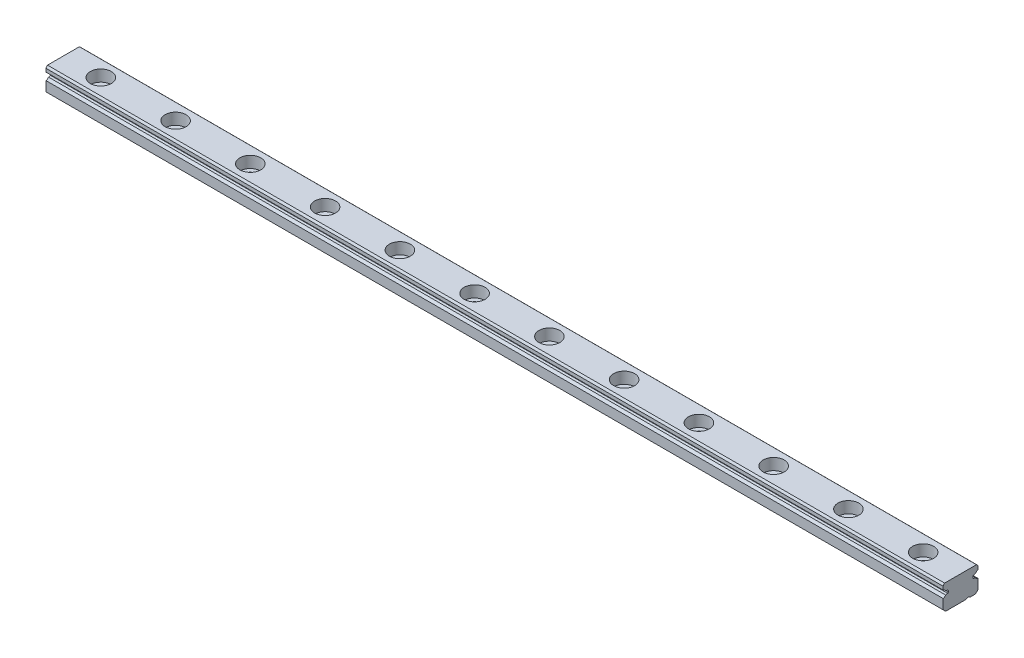
SolidWorks part; units mm, degrees
ref_plane "Front Plane" through (0, 0, 0) normal (0, 0, 1) x (1, 0, 0)
ref_plane "Top Plane" through (0, 0, 0) normal (0, 1, 0) x (1, 0, 0)
ref_plane "Right Plane" through (0, 0, 0) normal (1, 0, 0) x (0, 0, -1)
sketch "Sketch1" plane through (0, 0, 0) normal (1, 0, 0) x (0, 0, -1)
  line L0 (-3.5, 0.5) -> (-3, 0)
  line L1 (-3, 0) -> (3, 0)
  line L2 (3, 0) -> (3.5, 0.5)
  line L3 (3.5, 0.5) -> (3.5, 2.4652)
  line L4 (2.9999, 2.826) -> (2.572, 2.9015)
  line L5 (2.45, 3.051) -> (2.45, 3.349)
  line L6 (2.572, 3.4985) -> (2.9999, 3.574)
  line L7 (3.5, 3.9348) -> (3.5, 4.6)
  line L8 (3.2, 5) -> (-3.2, 5)
  line L9 (-3.5, 4.6) -> (-3.5, 3.9348)
  line L10 (-2.9999, 3.574) -> (-2.572, 3.4985)
  line L11 (-2.45, 3.349) -> (-2.45, 3.051)
  line L12 (-2.572, 2.9015) -> (-2.9999, 2.826)
  line L13 (-3.5, 2.4652) -> (-3.5, 0.5)
  arc A0 (3.5, 2.4652) -> (2.9999, 2.826) centre (3.65, 3.2) cw
  arc A1 (2.572, 2.9015) -> (2.45, 3.051) centre (2.8118, 3.2216) cw
  arc A2 (2.45, 3.349) -> (2.572, 3.4985) centre (2.8118, 3.1784) cw
  arc A3 (2.9999, 3.574) -> (3.5, 3.9348) centre (3.65, 3.2) cw
  arc A4 (3.5, 4.6) -> (3.2, 5) centre (2.7421, 4.344) ccw
  arc A5 (-3.2, 5) -> (-3.5, 4.6) centre (-2.7421, 4.344) ccw
  arc A6 (-3.5, 3.9348) -> (-2.9999, 3.574) centre (-3.65, 3.2) cw
  arc A7 (-2.572, 3.4985) -> (-2.45, 3.349) centre (-2.8118, 3.1784) cw
  arc A8 (-2.45, 3.051) -> (-2.572, 2.9015) centre (-2.8118, 3.2216) cw
  arc A9 (-2.9999, 2.826) -> (-3.5, 2.4652) centre (-3.65, 3.2) cw
extrude "Extrude1" add sketch "Sketch1" along normal blind 180
sketch "Sketch2" plane through (0, 0, 0) normal (0, 0, -1) x (-1, 0, 0)
  line L0 (-7.5, 5) -> (-5.4, 5)
  line L1 (-5.4, 5) -> (-5.4, 2.7)
  line L2 (-5.4, 2.7) -> (-6.3, 2.7)
  line L3 (-6.3, 2.7) -> (-6.3, 0.2)
  line L4 (-6.3, 0.2) -> (-6.1, 0)
  line L5 (-6.1, 0) -> (-7.5, 0)
  line L6 (-180, 5) -> (0, 5) construction
  line L7 (-7.5, 0) -> (-7.5, 5) construction
  line L8 (-180, 0) -> (0, 0) construction
  line L9 (0, 2.4652) -> (0, 0.5) construction
  line L10 (-7.5, 5) -> (-7.5, 0)
  dimension "D1" = 7.5
  dimension "D2" = 2.4
  dimension "D3" = 2.8
  dimension "D4" = 4.2
  dimension "D5" = 2.3
  dimension "D6" = 45
revolve "Cut-Revolve1" cut sketch "Sketch2" angle 360 about L7 reverse direction yes
sketch "Sketch3" plane through (45, 0, 0) normal (0, 0, -1) x (-1, 0, 0)
  line L0 (-127.5, 5) -> (-125.4, 5)
  line L1 (-125.4, 5) -> (-125.4, 2.7)
  line L2 (-125.4, 2.7) -> (-126.3, 2.7)
  line L3 (-126.3, 2.7) -> (-126.3, 0.2)
  line L4 (-126.3, 0.2) -> (-126.1, 0)
  line L5 (-126.1, 0) -> (-127.5, 0)
  line L6 (-135, 0) -> (45, 0) construction
  line L7 (-127.5, 0) -> (-127.5, 5) construction
  line L8 (-135, 5) -> (45, 5) construction
  line L9 (-135, 2.4652) -> (-135, 0.5) construction
  line L10 (-127.5, 5) -> (-127.5, 0)
  dimension "D1" = 7.5
  dimension "D2" = 2.4
  dimension "D3" = 2.8
  dimension "D4" = 45
  dimension "D5" = 4.2
  dimension "D6" = 2.3
revolve "Cut-Revolve2" cut sketch "Sketch3" angle 360 about L7 reverse direction yes
sketch "Sketch6" plane through (0, 0, 0) normal (1, 0, 0) x (0, 0, -1)
  circle A0 centre (1.5, -0.3) radius 0.5
extrude "Extrude2" cut sketch "Sketch6" along normal through all
ref_axis "Axis1" through (-3, 0, 0) along (1, 0, 0)
pattern_linear "LPattern1" count 11 spacing 15 along (-1, 0, 0) of "Cut-Revolve2"
